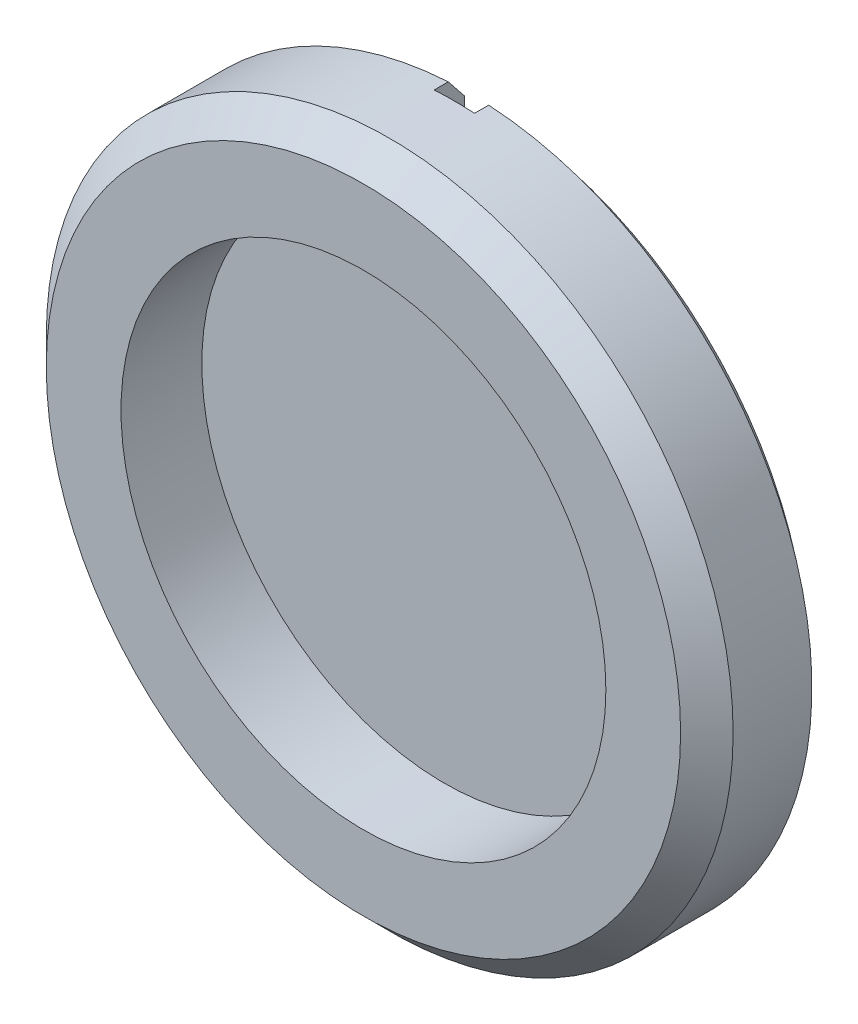
SolidWorks part; units mm, degrees
material "Alliage de zinc AC41A, brut"
ref_plane "Plan de face" through (0, 0, 0) normal (0, 0, 1) x (1, 0, 0)
ref_plane "Plan de dessus" through (0, 0, 0) normal (0, 1, 0) x (1, 0, 0)
ref_plane "Plan de droite" through (0, 0, 0) normal (1, 0, 0) x (0, 0, -1)
sketch "Esquisse1" plane through (0, 0, 0) normal (0, 0, 1) x (1, 0, 0)
  circle A0 centre (0, 0) radius 8.5
  dimension "D1" = 17
extrude "Boss.-Extru.1" add sketch "Esquisse1" along normal blind 3
cosmetic thread "Cosmetic Thread1" parameters "D2"=16
sketch "Esquisse4" plane through (0, 0, 3) normal (0, 0, 1) x (1, 0, 0)
  circle A0 centre (0, 0) radius 6
  dimension "D1" = 12
extrude "Enlèv. mat.-Extru.1" cut sketch "Esquisse4" against normal blind 2
sketch "Esquisse5" plane through (0, 0, 0) normal (0, 0, -1) x (-1, 0, 0)
  line L1 (-0.5, -8.5) -> (0.5, -8.5)
  line L2 (-0.5, -8.5) -> (-0.5, 8.5)
  line L3 (-0.5, 8.5) -> (0.5, 8.5)
  line L4 (0.5, -8.5) -> (0.5, 8.5)
  point P4 (0.5, 0)
  point P6 (0, 8.5)
  dimension "D1" = 17
  dimension "D2" = 1
extrude "Enlèv. mat.-Extru.2" cut sketch "Esquisse5" against normal blind 0.75
sketch "Esquisse6" plane through (0, 0, 0) normal (0, 1, 0) x (1, 0, 0)
  line L0 (-8, 0) -> (-8.5, -0.4)
  line L1 (8.5, -3) -> (-8.5, -3) construction
  line L2 (8.5, -3) -> (8.5, 0) construction
  line L3 (8.5, 0) -> (-8.5, 0) construction
  line L4 (-8.5, -3) -> (-8.5, 0) construction
  line L5 (-8.5, -2.35) -> (-7.85, -3)
  line L6 (-8.5, -0.4) -> (-8.5, 0)
  line L7 (-8.5, 0) -> (-8, 0)
  line L8 (-8.5, -2.35) -> (-8.5, -3)
  line L9 (-8.5, -3) -> (-7.85, -3)
  line L10 (0, 0) -> (0, -3) construction
  point P4 (0, 0)
  dimension "D1" = 17
  dimension "D2" = 3
  dimension "D3" = 0.5
  dimension "D4" = 0.4
  dimension "D5" = 0.65
  dimension "D6" = 0.65
revolve "Enlèvement de matière-Révolution1" cut sketch "Esquisse6" angle 360 about L10
